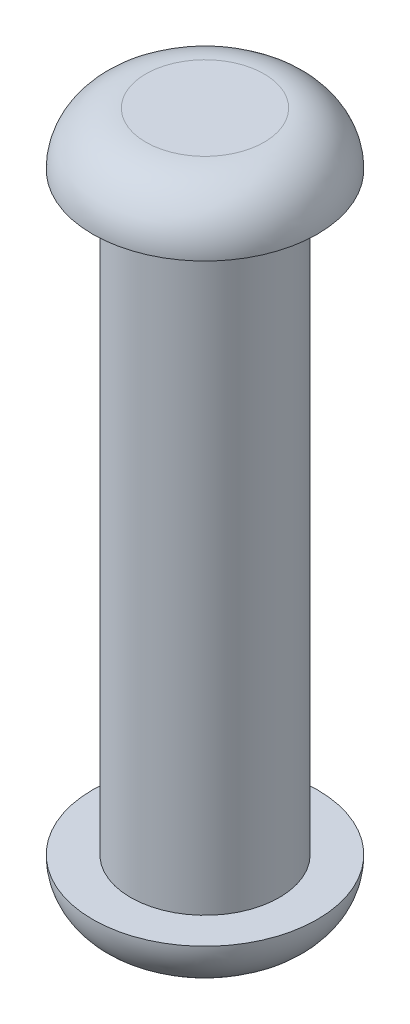
SolidWorks part; units mm, degrees
ref_plane "Front Plane" through (0, 0, 0) normal (0, 0, 1) x (1, 0, 0)
ref_plane "Top Plane" through (0, 0, 0) normal (0, 1, 0) x (1, 0, 0)
ref_plane "Right Plane" through (0, 0, 0) normal (1, 0, 0) x (0, 0, -1)
sketch "Sketch1" plane through (0, 0, 0) normal (0, 1, 0) x (1, 0, 0)
  circle A0 centre (0, 0) radius 0.49
  dimension "D1" = 0.98
extrude "Boss-Extrude1" add sketch "Sketch1" along normal blind 3.91
sketch "Sketch2" plane through (0, 3.91, 0) normal (0, 1, 0) x (1, 0, 0)
  circle A2 centre (0, 0) radius 0.74
  dimension "D1" = 1.48
extrude "Boss-Extrude2" add sketch "Sketch2" along normal blind 0.35
fillet "Fillet1" radius 0.35 1 edges at (0, 4.26, 0.74)
sketch "Sketch4" plane through (0, 0, 0) normal (0, -1, 0) x (1, 0, 0)
  circle A0 centre (0, 0) radius 0.74
  dimension "D1" = 1.48
extrude "Boss-Extrude3" add sketch "Sketch4" along normal blind 0.35
fillet "Fillet2" radius 0.35 1 edges at (0, -0.35, -0.74)
scale "Scale1" bodies to scale 103 scale about centroid uniform scaling yes scale factor 1.5
scale "Scale2" bodies to scale 104 scale about centroid uniform scaling yes scale factor 3.394558
